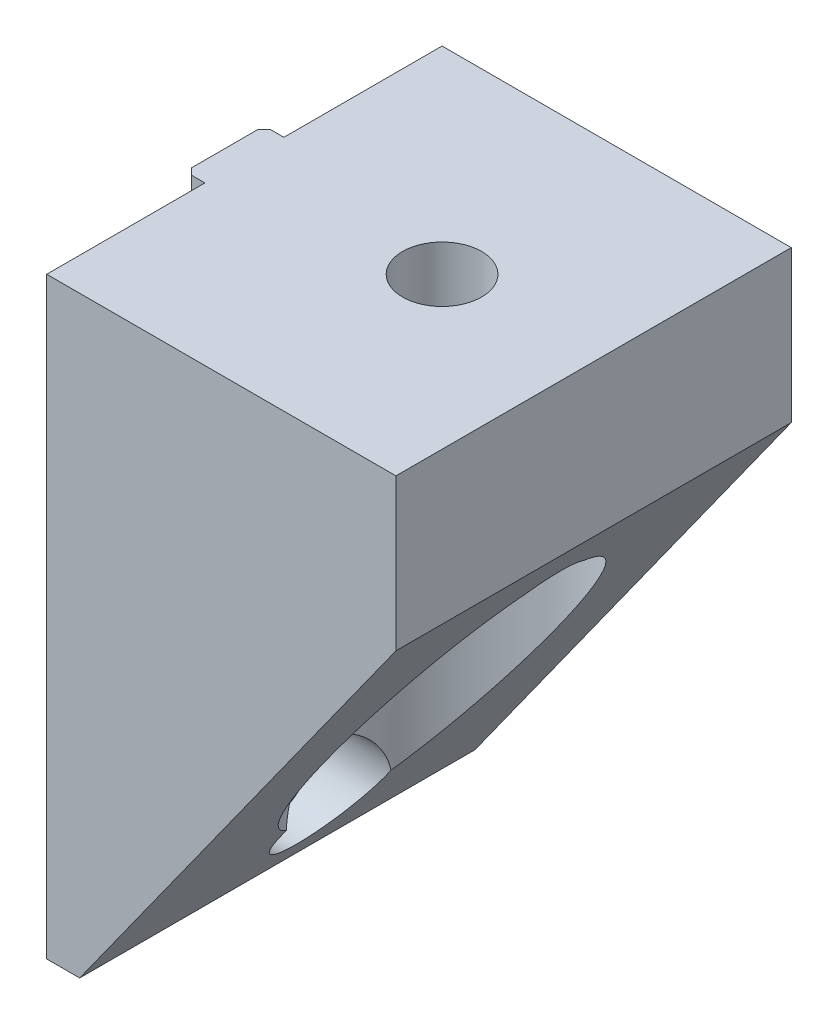
SolidWorks part; units mm, degrees
ref_plane "Płaszczyzna przednia" through (0, 0, 0) normal (0, 0, 1) x (1, 0, 0)
ref_plane "Płaszczyzna górna" through (0, 0, 0) normal (0, 1, 0) x (1, 0, 0)
ref_plane "Płaszczyzna prawa" through (0, 0, 0) normal (1, 0, 0) x (0, 0, -1)
sketch "Sketch1" plane through (0, 0, 0) normal (0, 0, 1) x (1, 0, 0)
  line L0 (0, 0) -> (0, 90)
  line L1 (0, 90) -> (53, 90)
  line L2 (53, 90) -> (53, 67)
  line L4 (0, 0) -> (5, 0)
  line L5 (53, 67) -> (5, 0)
  point P3 (0, 0)
  dimension "D1" = 5
  dimension "D2" = 90
  dimension "D3" = 53
  dimension "D4" = 23
extrude "Boss-Extrude1" add sketch "Sketch1" along normal blind 60
sketch "Sketch2" plane through (0, 0, 0) normal (0, 1, 0) x (1, 0, 0)
  line L0 (53, -60) -> (0, -60) construction
  line L1 (0, -60) -> (0, 0) construction
  circle A0 centre (30, -30) radius 6
  dimension "D3" = 12
  dimension "D1" = 30
  dimension "D2" = 30
extrude "Cut-Extrude1" cut sketch "Sketch2" along normal through all both and the other way through all
sketch "Sketch3" plane through (0, 0, 0) normal (0, 1, 0) x (1, 0, 0)
  circle A0 centre (30, -30) radius 17.6
  dimension "D1" = 35.2
extrude "Cut-Extrude2" cut sketch "Sketch3" along normal blind 78 contours A0
sketch "Sketch5" plane through (0, 0, 0) normal (1, 0, 0) x (0, 0, -1)
  line L0 (-60, 0) -> (-60, 67) construction
  line L1 (-60, 0) -> (0, 0) construction
  circle A0 centre (-30, 12) radius 4.1
  circle A1 centre (-30, 52) radius 4.1
  point P6 (0, 0)
  point P9 (0, 0)
  point P10 (0, 0)
  dimension "D2" = 8.2
  dimension "D1" = 30
  dimension "D3" = 12
  dimension "D4" = 40
extrude "Cut-Extrude4" cut sketch "Sketch5" along normal up to surface (12.8842 mm away) up to face at (30, 78, 47.6)
sketch "Sketch6" plane through (0, 0, 0) normal (1, 0, 0) x (0, 0, -1)
  circle A0 centre (-30, 52) radius 8
  circle A1 centre (-30, 12) radius 8
  dimension "D1" = 16
extrude "Cut-Extrude6" cut sketch "Sketch6" against normal blind 50 from surface starting at face at (53, 78.5, 30)
sketch "Sketch7" plane through (0, 0, 0) normal (1, 0, 0) x (0, 0, -1)
  line L0 (-60, 90) -> (0, 90) construction
  line L1 (-24, 90) -> (-36, 90)
  line L2 (-24, 90) -> (-24, 0)
  line L3 (-24, 0) -> (-36, 0)
  line L4 (-36, 90) -> (-36, 0)
  line L5 (-60, 0) -> (0, 0) construction
  dimension "D1" = 12
  dimension "D2" = 24
extrude "Boss-Extrude4" add sketch "Sketch7" against normal blind 3 from surface starting at face at (0, 12, 25.9)
extrude "Cut-Extrude7" cut sketch "Sketch5<2>" against normal through all both and the other way through all
sketch "Sketch5<2>" plane through (0, 0, 0) normal (1, 0, 0) x (0, 0, -1) same geometry as "Sketch5"
chamfer "Chamfer1" distance 1 angle 45 2 edges at (-3, 45, 24) (-3, 45, 36)
